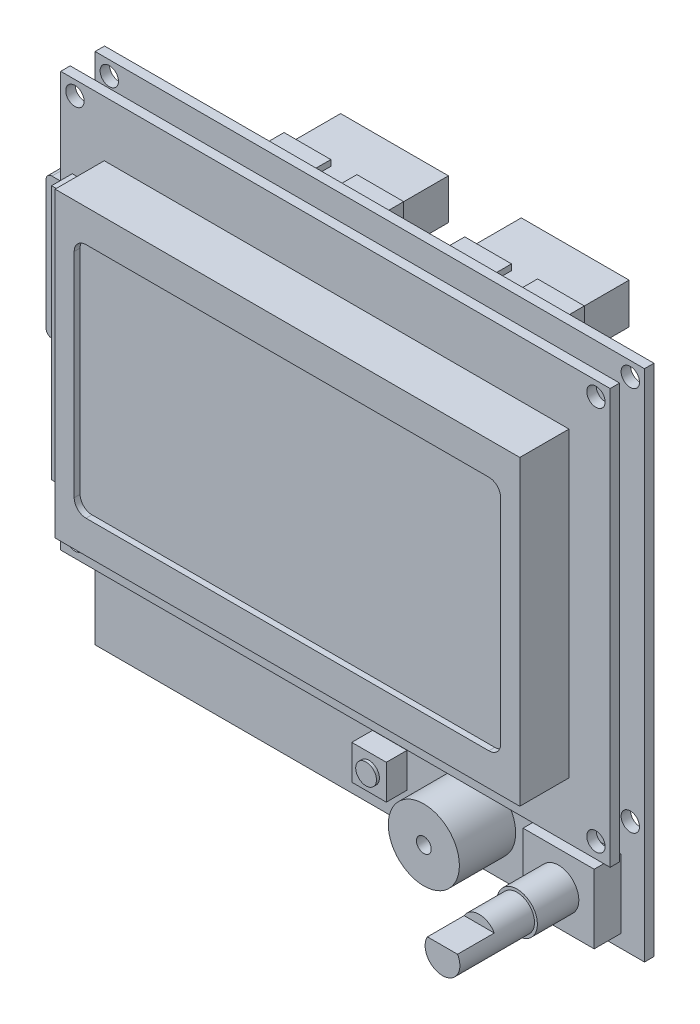
SolidWorks part; units mm, degrees
ref_plane "Front Plane" through (0, 0, 0) normal (0, 0, 1) x (1, 0, 0)
ref_plane "Top Plane" through (0, 0, 0) normal (0, 1, 0) x (1, 0, 0)
ref_plane "Right Plane" through (0, 0, 0) normal (1, 0, 0) x (0, 0, -1)
sketch "Sketch1" plane through (0, 0, 0) normal (0, 0, 1) x (1, 0, 0)
  line L1 (-46.375, -43.375) -> (46.375, -43.375)
  line L2 (-46.375, -43.375) -> (-46.375, 43.375)
  line L3 (-46.375, 43.375) -> (46.375, 43.375)
  line L4 (46.375, -43.375) -> (46.375, 43.375)
  line L6 (-43.975, 40.975) -> (43.975, 40.975) construction
  line L7 (-43.975, 40.975) -> (-43.975, -24.025) construction
  line L8 (-43.975, -24.025) -> (43.975, -24.025) construction
  line L9 (43.975, 40.975) -> (43.975, -24.025) construction
  circle A0 centre (-43.975, 40.975) radius 1.55
  circle A1 centre (43.975, 40.975) radius 1.55
  circle A2 centre (43.975, -24.025) radius 1.55
  circle A3 centre (-43.975, -24.025) radius 1.55
  point P5 (0, 43.375)
  point P6 (-46.375, 0)
  dimension "D3" = 3.1
  dimension "D1" = 86.75
  dimension "D2" = 92.75
  dimension "D4" = 2.4
  dimension "D5" = 2.4
  dimension "D6" = 2.4
  dimension "D7" = 65
extrude "Boss-Extrude1 - First PCB" add sketch "Sketch1" along normal blind 1.6
sketch "Sketch2" plane through (0, 0, 1.6) normal (0, 0, 1) x (1, 0, 0)
  line L0 (-46.375, -43.375) -> (46.375, -43.375) construction
  line L1 (-46.375, -43.375) -> (-46.375, 43.375) construction
  circle A0 centre (18.625, -35.375) radius 6
  dimension "D1" = 12
  dimension "D2" = 8
  dimension "D3" = 65
extrude "Boss-Extrude2 - Speaker" add sketch "Sketch2" along normal blind 9.5
sketch "Sketch15" plane through (0, 0, 11.1) normal (0, 0, 1) x (1, 0, 0)
  circle A0 centre (18.625, -35.375) radius 1.25
  dimension "D1" = 2.5
extrude "Cut-Extrude1 - Speaker Hole" cut sketch "Sketch15" against normal blind 5
sketch "Sketch3" plane through (0, 0, 1.6) normal (0, 0, 1) x (-1, 0, 0)
  line L1 (-42.375, 41.2) -> (-30.375, 41.2)
  line L2 (-42.375, 41.2) -> (-42.375, 29.55)
  line L3 (-42.375, 29.55) -> (-30.375, 29.55)
  line L4 (-30.375, 41.2) -> (-30.375, 29.55)
  line L8 (-30.375, 35.375) -> (-18.625, 35.375) construction
  line L10 (-36.375, 41.2) -> (-36.375, 29.55) construction
  line L11 (-46.375, 43.375) -> (-46.375, -43.375) construction
  circle A1 centre (-18.625, 35.375) radius 6 construction
  point P19 (-13.8797, 31.7032)
  dimension "D1" = 11.65
  dimension "D2" = 12
  dimension "D3" = 10
extrude "Boss-Extrude3 - Rotary Switch" add sketch "Sketch3" along normal blind 4.5
sketch "Sketch4" plane through (0, 0, 1.6) normal (0, 0, 1) x (-1, 0, 0)
  line L0 (-3.375, 38.29) -> (-3.375, 32.46) construction
  line L1 (-6.29, 38.29) -> (-0.46, 38.29)
  line L2 (-6.29, 38.29) -> (-6.29, 32.46)
  line L3 (-6.29, 32.46) -> (-0.46, 32.46)
  line L4 (-0.46, 38.29) -> (-0.46, 32.46)
  line L5 (-6.29, 35.375) -> (-0.46, 35.375) construction
  line L6 (-6.29, 35.375) -> (-18.625, 35.375) construction
  line L15 (-46.375, 43.375) -> (-46.375, -43.375) construction
  point P8 (-3.375, 35.375)
  dimension "D1" = 5.83
  dimension "D2" = 5.83
  dimension "D3" = 43
extrude "Boss-Extrude4 - Reset Switch" add sketch "Sketch4" along normal blind 3.5
sketch "Sketch5" plane through (0, 0, 5.1) normal (0, 0, 1) x (-1, 0, 0)
  line L1 (-6.29, 38.29) -> (-0.46, 32.46) construction
  line L2 (-0.46, 38.29) -> (-6.29, 32.46) construction
  circle A0 centre (-3.375, 35.375) radius 1.75
  dimension "D1" = 3.5
extrude "Boss-Extrude5 - Reset Button" add sketch "Sketch5" along normal blind 0.5
sketch "Sketch16" plane through (0, 0, 6.1) normal (0, 0, 1) x (1, 0, 0)
  line L0 (30.375, -29.55) -> (30.375, -41.2) construction
  line L1 (42.375, -29.55) -> (30.375, -29.55) construction
  circle A0 centre (36.375, -35.375) radius 3.415
  point P4 (30.375, -35.375)
  point P7 (36.375, -29.55)
  dimension "D1" = 6.83
extrude "Boss-Extrude6 - Rotary Switch" add sketch "Sketch16" along normal blind 7
sketch "Sketch17" plane through (0, 0, 13.1) normal (0, 0, 1) x (1, 0, 0)
  circle A0 centre (36.375, -35.375) radius 2.935
  dimension "D1" = 5.87
extrude "Boss-Extrude7 - Rotary Switch" add sketch "Sketch17" along normal blind 6.4
sketch "Sketch18" plane through (0, 0, 19.5) normal (0, 0, 1) x (1, 0, 0)
  line L0 (33.8318, -33.91) -> (38.9182, -33.91)
  arc A0 (33.8318, -33.91) -> (38.9182, -33.91) centre (36.375, -35.375) ccw
  circle A1 centre (36.375, -35.375) radius 2.935 construction
  point P6 (36.375, -38.31)
  dimension "D1" = 4.4
extrude "Boss-Extrude8 - Rotary Switch" add sketch "Sketch18" along normal offset from surface (6.2 mm away) 24.1 up to face at (36.375, -35.375, 1.6) offset beyond the face yes
sketch "Sketch9" plane through (0, 0, 0) normal (0, 0, -1) x (1, 0, 0)
  line L0 (-46.375, -43.375) -> (46.375, -43.375) construction
  line L1 (-46.125, 5.425) -> (-27.875, 5.425)
  line L2 (-46.125, 5.425) -> (-46.125, -20.975)
  line L3 (-46.125, -20.975) -> (-20.375, -20.975)
  line L4 (-20.375, 3.425) -> (-20.375, -20.975)
  line L6 (-20.375, 3.425) -> (-25.875, 3.425)
  line L7 (-25.875, 3.425) -> (-27.875, 5.425)
  line L8 (-46.375, -43.375) -> (-46.375, 43.375) construction
  dimension "D1" = 22.4
  dimension "D2" = 26.4
  dimension "D3" = 0.25
  dimension "D4" = 18.25
  dimension "D5" = 2
  dimension "D6" = 45
  dimension "D7" = 25.75
extrude "Boss-Extrude9 - SD Card Slot" add sketch "Sketch9" along normal blind 3
sketch "Sketch19" plane through (0, 0, 1.6) normal (0, 0, 1) x (1, 0, 0)
  line L0 (-46.375, 43.375) -> (-46.375, -43.375) construction
  line L1 (-33.375, -22.875) -> (16.625, -22.875)
  line L2 (-33.375, -22.875) -> (-33.375, -25.375)
  line L3 (-33.375, -25.375) -> (16.625, -25.375)
  line L4 (16.625, -22.875) -> (16.625, -25.375)
  line L5 (-46.375, -43.375) -> (46.375, -43.375) construction
  dimension "D1" = 2.5
  dimension "D2" = 50
  dimension "D3" = 13
  dimension "D4" = 18
extrude "Boss-Extrude10 - Connector" add sketch "Sketch19" along normal blind 4.2
sketch "Sketch11" plane through (0, -2, 5.8) normal (0, 0, -1) x (1, 0, 0)
  line L1 (46.375, 24.625) -> (-46.375, 24.625)
  line L2 (46.375, 24.625) -> (46.375, -45.375)
  line L3 (46.375, -45.375) -> (-46.375, -45.375)
  line L4 (-46.375, 24.625) -> (-46.375, -45.375)
  line L8 (46.375, 41.375) -> (46.375, -45.375) construction
  circle A0 centre (-43.975, -42.975) radius 1.55 construction
  circle A1 centre (-43.975, -42.975) radius 1.55
  circle A2 centre (-43.975, 22.025) radius 1.55 construction
  circle A3 centre (43.975, -42.975) radius 1.55 construction
  circle A4 centre (43.975, 22.025) radius 1.55 construction
  circle A5 centre (-43.975, 22.025) radius 1.55
  circle A6 centre (43.975, -42.975) radius 1.55
  circle A7 centre (43.975, 22.025) radius 1.55
  dimension "D2" = 70
extrude "Boss-Extrude11 - Upper PCB" add sketch "Sketch11" against normal blind 1.6
sketch "Sketch12" plane through (0, 0, 7.4) normal (0, 0, 1) x (-1, 0, 0)
  line L1 (-39.425, 17.025) -> (39.025, 17.025)
  line L2 (-39.425, 17.025) -> (-39.425, -33.975)
  line L3 (-39.425, -33.975) -> (39.025, -33.975)
  line L4 (39.025, 17.025) -> (39.025, -33.975)
  line L6 (46.375, -43.375) -> (-46.375, -43.375) construction
  line L7 (46.375, 26.625) -> (46.375, -43.375) construction
  dimension "D1" = 51
  dimension "D2" = 78.45
  dimension "D3" = 9.4
  dimension "D4" = 7.35
extrude "Boss-Extrude12 - LCD" add sketch "Sketch12" along normal blind 8.3
sketch "Sketch24" plane through (0, 0, 7.4) normal (0, 0, 1) x (1, 0, 0)
  line L0 (-39.025, 33.975) -> (-39.025, -17.025) construction
  line L1 (-39.025, 29.375) -> (-44.425, 29.375)
  line L2 (-39.025, 29.375) -> (-39.025, -13.625)
  line L3 (-39.025, -13.625) -> (-44.425, -13.625)
  line L4 (-44.425, 29.375) -> (-44.425, -13.625)
  line L5 (39.425, 33.975) -> (-39.025, 33.975) construction
  dimension "D1" = 5.4
  dimension "D2" = 43
  dimension "D3" = 4.6
extrude "Boss-Extrude13 - LCD Bumpout" add sketch "Sketch24" along normal blind 3.5
sketch "Sketch13" plane through (0, 0, 15.7) normal (0, 0, 1) x (-1, 0, 0)
  line L0 (-0.2, 17.025) -> (-0.2, -33.975) construction
  line L2 (-39.425, -33.975) -> (39.025, -33.975) construction
  line L3 (-39.425, -8.475) -> (39.025, -8.475) construction
  line L4 (-39.425, 17.025) -> (-39.425, -33.975) construction
  line L5 (39.025, -33.975) -> (39.025, 17.025) construction
  line L6 (-0.2, 11.525) -> (-0.2, -28.475) construction
  line L7 (-34.2, 11.525) -> (33.8, 11.525)
  line L8 (-36.2, 9.525) -> (-36.2, -26.475)
  line L9 (-34.2, -28.475) -> (33.8, -28.475)
  line L10 (35.8, 9.525) -> (35.8, -26.475)
  line L11 (-39.425, 17.025) -> (39.025, 17.025) construction
  arc A8 (33.8, 11.525) -> (35.8, 9.525) centre (33.8, 9.525) cw
  arc A9 (-36.2, -26.475) -> (-34.2, -28.475) centre (-34.2, -26.475) ccw
  arc A10 (-34.2, 11.525) -> (-36.2, 9.525) centre (-34.2, 9.525) ccw
  arc A11 (33.8, -28.475) -> (35.8, -26.475) centre (33.8, -26.475) ccw
  point P18 (-0.2, -8.475)
  point P19 (-0.2, -8.475)
  point P62 (-36.2, -28.475)
  point P65 (-36.2, 11.525)
  dimension "D8" = 2
  dimension "D1" = 40
  dimension "D2" = 72
extrude "Cut-Extrude2 - Screen Recess" cut sketch "Sketch13" against normal blind 1 contours L10 L7 L8 L9 region at (0.2, 8.475, 15.7)
sketch "Sketch21" plane through (0, 0, 0) normal (0, 0, -1) x (-1, 0, 0)
  line L0 (-46.375, -43.375) -> (-46.375, 43.375) construction
  line L1 (-25.625, 36.875) -> (-5.425, 36.875)
  line L2 (-25.625, 36.875) -> (-25.625, 28.025)
  line L3 (-25.625, 28.025) -> (-5.425, 28.025)
  line L4 (-5.425, 36.875) -> (-5.425, 28.025)
  line L5 (4.875, 36.875) -> (25.075, 36.875)
  line L6 (4.875, 36.875) -> (4.875, 28.025)
  line L7 (4.875, 28.025) -> (25.075, 28.025)
  line L8 (25.075, 36.875) -> (25.075, 28.025)
  line L9 (-46.375, 43.375) -> (46.375, 43.375) construction
  line L10 (-24.625, 35.875) -> (-6.425, 35.875)
  line L11 (-6.425, 35.875) -> (-6.425, 29.025)
  line L12 (-24.625, 29.025) -> (-6.425, 29.025)
  line L13 (-24.625, 35.875) -> (-24.625, 29.025)
  line L14 (5.875, 35.875) -> (24.075, 35.875)
  line L15 (24.075, 35.875) -> (24.075, 29.025)
  line L16 (5.875, 29.025) -> (24.075, 29.025)
  line L17 (5.875, 35.875) -> (5.875, 29.025)
  dimension "D1" = 20.2
  dimension "D2" = 10.3
  dimension "D3" = 8.85
  dimension "D4" = 20.75
  dimension "D5" = 6.5
  dimension "D6" = 1
  dimension "D7" = 1
extrude "Boss-Extrude14 - Connectors" add sketch "Sketch21" along normal blind 9
sketch "Sketch22" plane through (0, 0, 0) normal (0, 0, -1) x (-1, 0, 0)
  line L4 (-24.625, 35.875) -> (-24.625, 29.025)
  line L5 (-24.625, 29.025) -> (-6.425, 29.025)
  line L6 (-6.425, 29.025) -> (-6.425, 35.875)
  line L7 (-6.425, 35.875) -> (-24.625, 35.875)
  line L8 (-24.625, 35.875) -> (-24.625, 29.025)
  line L9 (-24.625, 29.025) -> (-6.425, 29.025)
  line L10 (-6.425, 29.025) -> (-6.425, 35.875)
  line L11 (-6.425, 35.875) -> (-24.625, 35.875)
  line L12 (5.875, 35.875) -> (5.875, 29.025)
  line L13 (5.875, 29.025) -> (24.075, 29.025)
  line L14 (24.075, 29.025) -> (24.075, 35.875)
  line L15 (24.075, 35.875) -> (5.875, 35.875)
  line L16 (5.875, 35.875) -> (5.875, 29.025)
  line L17 (5.875, 29.025) -> (24.075, 29.025)
  line L18 (24.075, 29.025) -> (24.075, 35.875)
  line L19 (24.075, 35.875) -> (5.875, 35.875)
  dimension "D1" = 0
  dimension "D2" = 0
extrude "Boss-Extrude15 - Connector Recess" add sketch "Sketch22" along normal blind 2.55
sketch "Sketch23" plane through (0, 0, -9) normal (0, 0, -1) x (-1, 0, 0)
  line L0 (-5.425, 36.875) -> (-25.625, 36.875) construction
  line L1 (-17.725, 36.875) -> (-13.325, 36.875)
  line L2 (-17.725, 36.875) -> (-17.725, 35.875)
  line L3 (-17.725, 35.875) -> (-13.325, 35.875)
  line L4 (-13.325, 36.875) -> (-13.325, 35.875)
  line L5 (-6.425, 35.875) -> (-24.625, 35.875) construction
  line L6 (25.075, 36.875) -> (4.875, 36.875) construction
  line L7 (12.775, 36.875) -> (17.175, 36.875)
  line L8 (12.775, 36.875) -> (12.775, 35.875)
  line L9 (12.775, 35.875) -> (17.175, 35.875)
  line L10 (17.175, 36.875) -> (17.175, 35.875)
  line L11 (24.075, 35.875) -> (5.875, 35.875) construction
  line L12 (14.975, 29.025) -> (14.975, 36.875) construction
  line L13 (5.875, 29.025) -> (24.075, 29.025) construction
  line L14 (-15.525, 29.025) -> (-15.525, 36.875) construction
  line L15 (-24.625, 29.025) -> (-6.425, 29.025) construction
  point P20 (14.975, 36.875)
  point P25 (-15.525, 36.875)
  dimension "D1" = 4.4
extrude "Cut-Extrude3 - Connector Notch" cut sketch "Sketch23" against normal up to surface (6.45 mm away) up to face at (15.525, 32.45, -2.55)
sketch "Sketch20" plane through (-46.125, 0, 0) normal (-1, 0, 0) x (0, 0, 1)
  line L0 (1.6, 43.375) -> (1.6, -43.375) construction
  line L1 (-2.423, 19.65) -> (-0.27, 19.65)
  line L2 (-2.423, 19.65) -> (-2.423, -4.1)
  line L3 (-2.423, -4.1) -> (-0.27, -4.1)
  line L4 (-0.27, 19.65) -> (-0.27, -4.1)
  line L5 (-3, 7.775) -> (-2.423, 7.775) construction
  line L6 (-3, -5.425) -> (-3, 20.975) construction
  dimension "D1" = 23.75
  dimension "D2" = 2.153
  dimension "D3" = 1.87
extrude "Boss-Extrude16 - SD Card" add sketch "Sketch20" along normal blind 10.4
fillet "Fillet1 - SD Card" radius 1 2 edges at (-56.525, -4.1, -1.3465) (-56.525, 19.65, -1.3465)
sketch "Croquis1" plane through (0, 0, -2.55) normal (0, 0, -1) x (-1, 0, 0)
  line L1 (-24.625, 35.875) -> (-6.425, 35.875)
  line L2 (-24.625, 35.875) -> (-24.625, 29.025)
  line L3 (-24.625, 29.025) -> (-6.425, 29.025)
  line L4 (-6.425, 35.875) -> (-6.425, 29.025)
  line L5 (5.875, 35.875) -> (24.075, 35.875)
  line L6 (5.875, 35.875) -> (5.875, 29.025)
  line L7 (5.875, 29.025) -> (24.075, 29.025)
  line L8 (24.075, 35.875) -> (24.075, 29.025)
extrude "Saliente-Extruir1" add sketch "Croquis1" along normal blind 15
